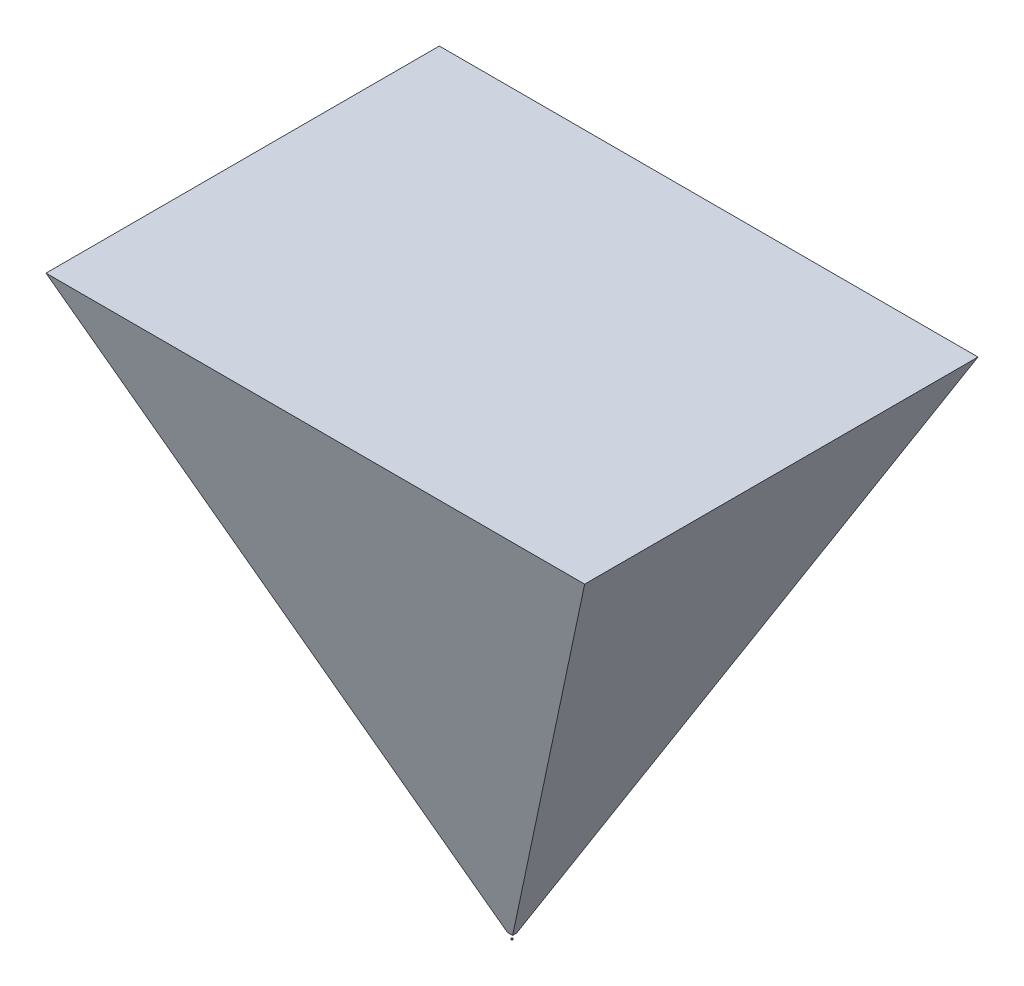
SolidWorks part; units mm, degrees
material "ABS PC"
ref_plane "Vorne" through (0, 0, 0) normal (0, 0, 1) x (1, 0, 0)
ref_plane "Oben" through (0, 0, 0) normal (0, 1, 0) x (1, 0, 0)
ref_plane "Rechts" through (0, 0, 0) normal (1, 0, 0) x (0, 0, -1)
sketch "Skizze3" plane through (0, 0, 0) normal (0, 0, 1) x (1, 0, 0)
  line L0 (0, 0) -> (0, -2.1568) construction
  line L1 (1, 0.8) -> (2.75, 0.8)
  line L2 (2.75, 0.8) -> (2.75, -2.55)
  line L3 (2.75, -2.55) -> (2.1, -2.55)
  line L4 (1, 0.8) -> (0.625, 0.425)
  line L5 (0.8125, 0.6125) -> (0.8125, 0.8) construction
  line L6 (0.8125, 0.8) -> (1, 0.8) construction
  line L7 (2.1, -2.55) -> (1.8, -2.25)
  line L8 (2.1, -2.55) -> (2.1, -2.4) construction
  line L9 (2.1, -2.4) -> (1.95, -2.4) construction
  line L10 (0, -2.55) -> (0, 0.525)
  arc A0 (1.8, -2.25) -> (0, -2.55) centre (0, 3) cw
  arc A1 (0, 0.525) -> (0.625, 0.425) centre (0, -1.4781) cw
  dimension "D6" = 0.1
  dimension "D1" = 3.35
  dimension "D2" = 5.5
  dimension "D3" = 2
  dimension "D4" = 1.25
  dimension "D5" = 3.6
  dimension "D7" = 0.8
  dimension "D8" = 0.3
revolve "Body" add sketch "Skizze3" angle 360 about L0
sketch "Skizze4" plane through (0, 0, 0) normal (0, 0, 1) x (1, 0, 0)
  line L0 (0, 0) -> (0, 1.3093) construction
  line L1 (2.75, -2.55) -> (2.75, 0.8) construction
  line L2 (2.75, -0.2) -> (3, -0.2)
  line L3 (2.75, -0.2) -> (2.75, -1.2)
  line L4 (2.75, -1.2) -> (3, -1.2)
  line L5 (3, -0.2) -> (3, -1.2)
  line L6 (2.75, 0.8) -> (-2.75, 0.8) construction
  dimension "D1" = 2
  dimension "D2" = 1
  dimension "D3" = 6
revolve "Thread" add sketch "Skizze4" angle 360 about L0
sketch "Skizze5" plane through (0, 0, 0) normal (1, 0, 0) x (0, 0, -1)
  line L0 (0, 0) -> (0, -3.7681) construction
  line L1 (2.75, 0.8) -> (2.75, 0.35)
  line L2 (2.75, -0.2) -> (2.75, 0.8) construction
  line L3 (2.75, 0.35) -> (2.3, 0.8)
  line L4 (2.75, 0.8) -> (-2.75, 0.8) construction
  line L5 (2.3, 0.8) -> (2.75, 0.8)
  dimension "D1" = 0.45
revolve "Toolface" cut sketch "Skizze5" angle 60 about L0
pattern_circular "Kreismuster1" count 3 over 360 of "Toolface"
sketch "Skizze6" plane through (0, 0, 0) normal (1, 0, 0) x (0, 0, -1)
  line L0 (0, 0) -> (0, 10.2784) construction
  line L1 (-7.2794, 18.7078) -> (-735.2199, 2018.7078)
  line L2 (-735.2199, 2018.7078) -> (735.2199, 2018.7078)
  line L3 (-7.2794, 18.7078) -> (7.2794, 18.7078)
  line L4 (0, 2018.7078) -> (0, 18.7078) construction
  line L5 (-7.2794, 18.7078) -> (0, -1.2922) construction
  line L8 (7.2794, 18.7078) -> (735.2199, 2018.7078)
  point P3 (-0.625, 0.425)
  dimension "D1" = 2000
  dimension "D2" = 20
  dimension "D3" = 40
extrude "FOV - 3,6mm f/2,9" add sketch "Skizze6" along normal mid plane 3000 separate body
sketch "Skizze8" plane through (0, 0, 0) normal (0, 0, 1) x (1, 0, 0)
  line L0 (0, 0) -> (0, 233.3089) construction
  line L1 (-9.7405, 18.7078) -> (-1006.9037, 2018.7078)
  line L2 (1500, 18.7078) -> (-1500, 18.7078) construction
  line L3 (1500, 2018.7078) -> (-1500, 2018.7078) construction
  line L4 (-1006.9037, 2018.7078) -> (1006.9037, 2018.7078)
  line L5 (-9.7405, 18.7078) -> (9.7405, 18.7078)
  line L8 (9.7405, 18.7078) -> (1006.9037, 2018.7078)
  circle A0 centre (0, 0) radius 5
  point P9 (-0.625, 0.425)
  point P16 (0, 18.7078)
  point P17 (0, 2018.7078)
  dimension "D2" = 10
  dimension "D1" = 53
extrude "FOV2" cut sketch "Skizze8" against normal through all and the other way through all flip side to cut
